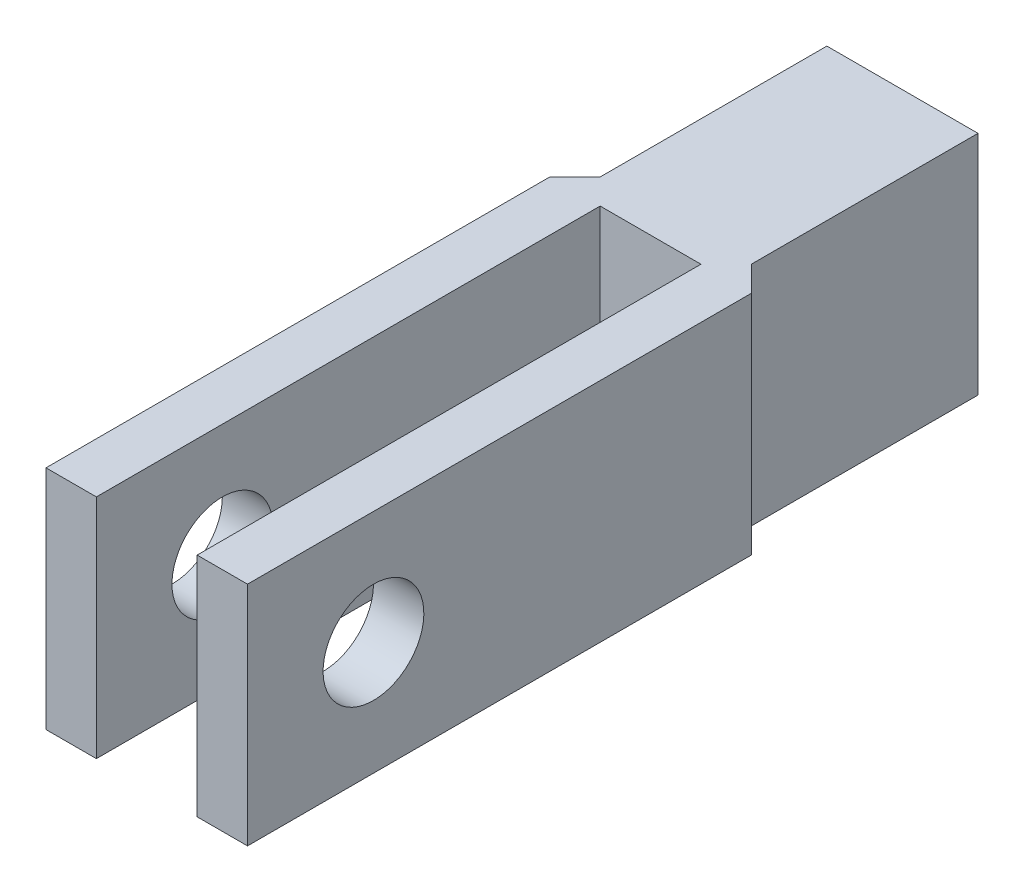
SolidWorks part; units mm, degrees
material "6061 Alloy"
ref_plane "Front Plane" through (0, 0, 0) normal (0, 0, 1) x (1, 0, 0)
ref_plane "Top Plane" through (0, 0, 0) normal (0, 1, 0) x (1, 0, 0)
ref_plane "Right Plane" through (0, 0, 0) normal (1, 0, 0) x (0, 0, -1)
sketch "Sketch1" plane through (0, 0, 0) normal (0, 0, 1) x (1, 0, 0)
  line L1 (-3, -4.5) -> (3, -4.5)
  line L2 (-3, -4.5) -> (-3, 4.5)
  line L3 (-3, 4.5) -> (3, 4.5)
  line L4 (3, -4.5) -> (3, 4.5)
  line L5 (-3, -4.5) -> (3, 4.5) construction
  line L6 (-3, 4.5) -> (3, -4.5) construction
  point P0 (0, 0)
  dimension "D1" = 9
  dimension "D2" = 6
extrude "Boss-Extrude1" add sketch "Sketch1" along normal blind 10
sketch "Sketch8" plane through (0, 0, 0) normal (0, 0, -1) x (-1, 0, 0)
  point P0 (0, 0)
hole_wizard "M4 Tapped Hole2" positions "Sketch9" profile "Sketch10" tap size "M4" standard "ISO"
sketch "Sketch9" plane through (0, 0, 0) normal (0, 0, -1) x (-1, 0, 0)
  point P0 (0, 0)
sketch "Sketch10" plane through (0, 0, 0) normal (1, 0, 0) x (0, 1, 0)
  line L0 (0, 0) -> (0, 8.9914)
  line L1 (0, 8.9914) -> (1.65, 8)
  line L2 (1.65, 8) -> (1.65, 0)
  line L5 (1.65, 0) -> (0, 0)
  line L10 (0, 8.9914) -> (-1.65, 8) construction
  line L11 (0, -6.35) -> (0, 107.95) construction
  dimension "Tap Drill Dia." = 3.3
  dimension "Tap Drill Depth" = 8
  dimension "Drill Angle" = 118
cosmetic thread "Hole Thread2" parameters "D1"=8, "D2"=4
sketch "Sketch11" plane through (0, 0, 10) normal (0, 0, 1) x (1, 0, 0)
  line L0 (-3, -4.5) -> (3, -4.5) construction
  line L1 (4, 4.5) -> (2, 4.5)
  line L2 (4, 4.5) -> (4, -4.5)
  line L3 (4, -4.5) -> (2, -4.5)
  line L4 (2, 4.5) -> (2, -4.5)
  line L5 (3, 4.5) -> (-3, 4.5) construction
  dimension "D1" = 2
  dimension "D2" = 2
extrude "Boss-Extrude5" add sketch "Sketch11" along normal blind 20
sketch "Sketch12" plane through (4, 0, 0) normal (1, 0, 0) x (0, 0, -1)
  line L0 (-10, 4.5) -> (0, 4.5) construction
  line L2 (-30, -4.5) -> (-30, 4.5) construction
  circle A0 centre (-25, 0) radius 2
  dimension "D2" = 4
  dimension "D1" = 4.5
  dimension "D3" = 5
extrude "Cut-Extrude1" cut sketch "Sketch12" against normal up to surface (2 mm away) up to face at (2, 0, 20)
mirror "Mirror1" about plane through (0, 0, 0) normal (1, 0, 0) of "Cut-Extrude1", "Boss-Extrude5"
chamfer "Chamfer1" distance 1 angle 45 1 edges at (3, 0, 10)
chamfer "Chamfer2" distance 1 angle 45 1 edges at (-3, 0, 10)
equation "\"Height\"=9"
equation "\"width\"=6"
equation "\"D2@Sketch1\"=\"width\""
equation "\"D1@Sketch1\"=\"Height\""
equation "\"D1@Sketch12\"=\"Height\"/2"
